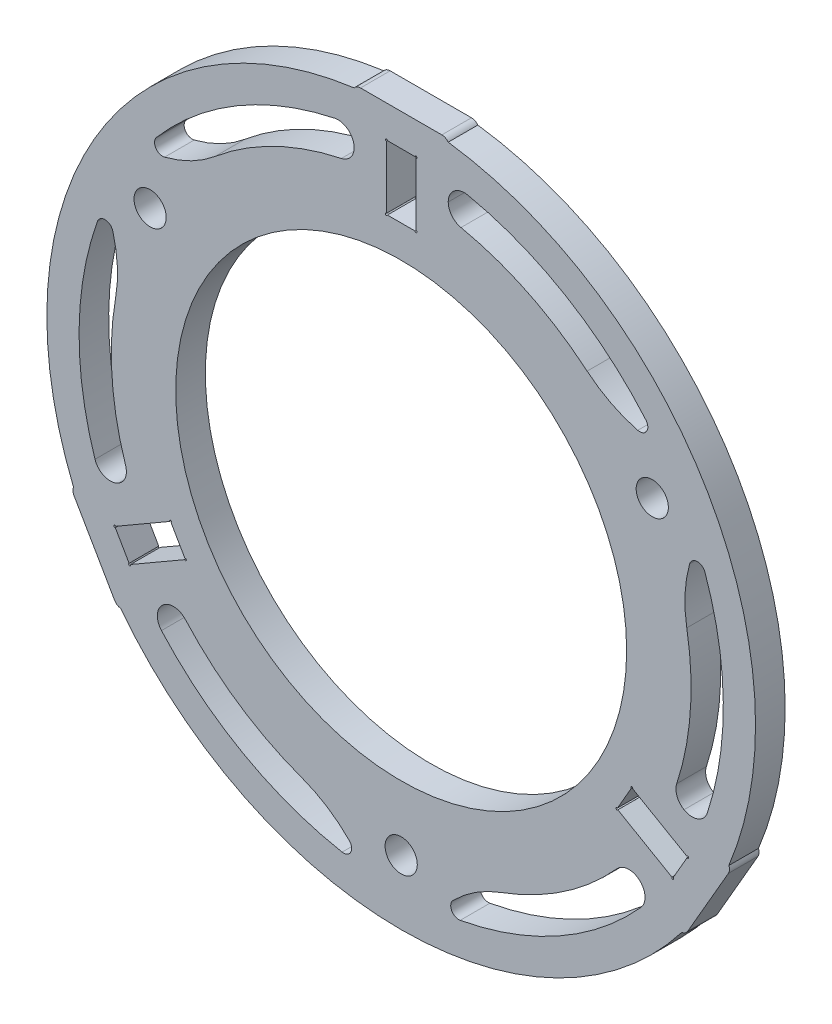
SolidWorks part; units mm, degrees
ref_plane "Front Plane" through (0, 0, 0) normal (0, 0, 1) x (1, 0, 0)
ref_plane "Top Plane" through (0, 0, 0) normal (0, 1, 0) x (1, 0, 0)
ref_plane "Right Plane" through (0, 0, 0) normal (1, 0, 0) x (0, 0, -1)
sketch "Sketch1" plane through (0, 0, 0) normal (0, 0, 1) x (1, 0, 0)
  line L0 (0, 0) -> (60.4919, 34.925) construction
  line L6 (0, 0) -> (50.8, 87.9882) construction
  line L7 (-44.45, 0) -> (44.45, 0) construction
  circle A0 centre (0, 0) radius 44.45
  circle A1 centre (0, 0) radius 69.85 construction
  arc A2 (-53.5519, 19.9579) -> (-9.4919, -56.3563) centre (0, 0) ccw
  arc A4 (9.4919, -56.3562) -> (53.5519, 19.9579) centre (0, 0) ccw
  arc A5 (44.06, 36.3983) -> (-44.06, 36.3983) centre (0, 0) ccw
  arc A6 (-28.575, 49.4934) -> (-44.06, 36.3983) centre (0, 0) ccw
  circle A8 centre (0, 0) radius 57.15 construction
  arc A10 (-28.575, -49.4934) -> (-9.4919, -56.3563) centre (0, 0) ccw
  arc A11 (57.15, 0) -> (53.5519, 19.9579) centre (0, 0) ccw
  circle A12 centre (50.8, 87.9882) radius 38.1 construction
  circle A13 centre (101.6, 0) radius 38.1 construction
  circle A14 centre (50.8, -87.9882) radius 38.1 construction
  circle A15 centre (-50.8, -87.9882) radius 38.1 construction
  circle A16 centre (-101.6, 0) radius 38.1 construction
  circle A17 centre (-50.8, 87.9882) radius 38.1 construction
  circle A25 centre (49.4934, 28.575) radius 3.175
  arc A26 (53.5519, 19.9579) -> (44.06, 36.3983) centre (49.4934, 28.575) ccw
  arc A27 (44.06, 36.3983) -> (28.575, 49.4934) centre (0, 0) ccw
  arc A28 (-9.4919, -56.3563) -> (9.4919, -56.3562) centre (0, -57.15) ccw
  circle A29 centre (0, -57.15) radius 3.175
  arc A30 (-44.06, 36.3983) -> (-53.5519, 19.9579) centre (-49.4934, 28.575) ccw
  circle A31 centre (-49.4934, 28.575) radius 3.175
  arc A32 (9.4919, -56.3562) -> (28.575, -49.4934) centre (0, 0) ccw
  arc A33 (-53.5519, 19.9579) -> (-57.15, 0) centre (0, 0) ccw
  point P7 (63.5, 0)
  point P12 (0, 0)
  point P36 (0, 0)
  point P49 (0, 0)
  point P53 (0, 0)
  point P64 (0, 0)
  dimension "D1" = 88.9
  dimension "D2" = 139.7
  dimension "D9" = 6
  dimension "D11" = 6.35
  dimension "D12" = 57.15
  dimension "D13" = 19.05
  dimension "D8" = 101.6
  dimension "D10" = 60
  dimension "D7" = 30
  dimension "D6" = 12.7
  dimension "D14" = 3
extrude "Boss-Extrude1" add sketch "Sketch1" along normal blind 5.842 contours A11 A6 A10 A0 region at (-56.2607, 32.4821, 0)
fillet "Fillet5" radius 25.4 6 edges at (44.06, 36.3983, 2.921) (9.4919, -56.3562, 2.921) (-9.4919, -56.3563, 2.921) (53.5519, 19.9579, 2.921) (-44.06, 36.3983, 2.921) (-53.5519, 19.9579, 2.921)
sketch "Sketch3" plane through (0, 0, 0) normal (0, 0, -1) x (-1, 0, 0)
  circle A0 centre (0, 0) radius 69.85
  circle A1 centre (0, 0) radius 63.5
  point P0 (0, 0)
  point P14 (66.7979, 20.4222)
  dimension "D1" = 6.35
extrude "Boss-Extrude3" add sketch "Sketch3" against normal up to surface (5.842 mm away) up to face at (-46.3184, 28.575, 5.842)
fillet "Fillet7" radius 1.5875 6 edges at (50.8754, 37.9992, 2.921) (58.346, 25.0598, 2.921) (7.4705, -63.059, 2.921) (-7.4705, -63.059, 2.921) (-58.346, 25.0598, 2.921) (-50.8754, 37.9992, 2.921)
sketch "Sketch5" plane through (0, 0, 5.842) normal (0, 0, 1) x (1, 0, 0)
  line L0 (0, 0) -> (0, 57.15) construction
  line L1 (-9.271, 69.85) -> (-9.271, 44.45)
  line L6 (2.921, 63.5) -> (-2.921, 50.8) construction
  line L7 (2.921, 50.8) -> (-2.921, 63.5) construction
  line L8 (9.271, 44.45) -> (-9.271, 44.45)
  line L9 (9.271, 69.85) -> (9.271, 44.45)
  line L10 (9.271, 69.85) -> (-9.271, 69.85)
  dimension "D1" = 57.15
  dimension "D2" = 5.842
  dimension "D3" = 12.7
extrude "Boss-Extrude4" add sketch "Sketch5" against normal up to surface (5.842 mm away) up to face at (-40.552, -23.4127, 0)
pattern_circular "CirPattern1" count 3 every 120 about axis through (0, 0, 5.842) along (0, 0, -1) of "Boss-Extrude4"
fillet "Fillet8" radius 1.5875 6 edges at (65.1274, -26.8961, 2.921) (55.8564, -42.9539, 2.921) (-55.8564, -42.9539, 2.921) (-65.1274, -26.8961, 2.921) (9.271, 69.85, 2.921) (-9.271, 69.85, 2.921)
sketch "Sketch7" plane through (0, 0, 5.842) normal (0, 0, 1) x (1, 0, 0)
  line L0 (0, 0) -> (0, 69.85) construction
  line L1 (8.0139, 69.85) -> (-8.0139, 69.85) construction
  line L3 (2.7226, 63.5) -> (-2.7226, 63.5)
  line L4 (2.921, 63.3016) -> (2.921, 50.9984)
  line L5 (2.7226, 50.8) -> (-2.7226, 50.8)
  line L6 (-2.921, 63.3016) -> (-2.921, 50.9984)
  line L7 (2.921, 63.5) -> (-2.921, 50.8) construction
  line L8 (2.921, 50.8) -> (-2.921, 63.5) construction
  arc A0 (-2.7226, 63.5) -> (-2.921, 63.3016) centre (-2.921, 63.5) ccw
  arc A1 (2.921, 63.3016) -> (2.7226, 63.5) centre (2.921, 63.5) ccw
  arc A2 (2.7226, 50.8) -> (2.921, 50.9984) centre (2.921, 50.8) ccw
  arc A3 (-2.921, 50.9984) -> (-2.7226, 50.8) centre (-2.921, 50.8) ccw
  point P5 (0, 57.15)
  point P21 (0, 0)
  dimension "D4" = 0.3969
  dimension "D5" = 0.3969
  dimension "D6" = 0.3969
  dimension "D7" = 0.3969
  dimension "D1" = 57.15
  dimension "D2" = 5.842
  dimension "D3" = 12.7
extrude "Cut-Extrude7" cut sketch "Sketch7" against normal through all
pattern_circular "CirPattern2" count 3 every 120 about axis through (0, 0, 203.4076) along (0, 0, -1) of "Cut-Extrude7"
fillet "Fillet9" radius 3.175 12 edges at (-59.0388, -23.3809, 2.921) (-53.4733, -20.1676, 2.921) (-49.7678, -39.4387, 2.921) (-44.2023, -36.2254, 2.921) (44.2023, -36.2254, 2.921) (49.7678, -39.4387, 2.921) (59.0388, -23.3809, 2.921) (53.4733, -20.1676, 2.921) (9.271, 56.393, 2.921) (9.271, 62.8196, 2.921) (-9.271, 62.8196, 2.921) (-9.271, 56.393, 2.921)
